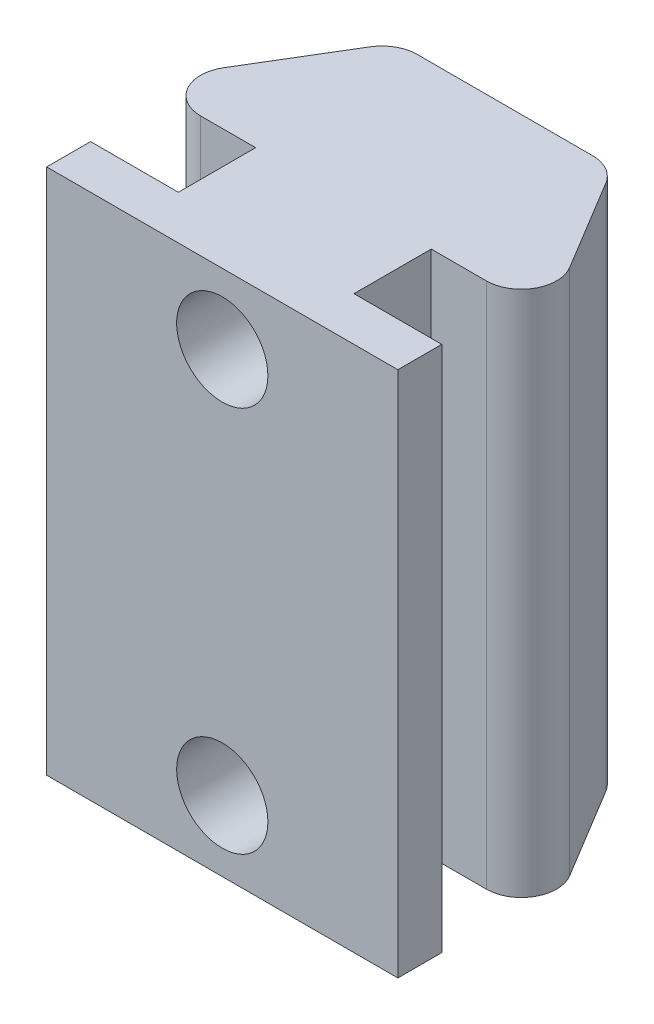
SolidWorks part; units mm, degrees
ref_plane "Front Plane" through (0, 0, 0) normal (0, 0, 1) x (1, 0, 0)
ref_plane "Top Plane" through (0, 0, 0) normal (0, 1, 0) x (1, 0, 0)
ref_plane "Right Plane" through (0, 0, 0) normal (1, 0, 0) x (0, 0, -1)
sketch "Sketch1" plane through (0, 0, 0) normal (0, 0, 1) x (1, 0, 0)
  line L0 (-6.35, 0) -> (6.35, 0) construction
  line L1 (-6.35, -9.525) -> (6.35, -9.525)
  line L2 (-6.35, -9.525) -> (-6.35, 9.525)
  line L3 (-6.35, 9.525) -> (6.35, 9.525)
  line L4 (6.35, -9.525) -> (6.35, 9.525)
  line L5 (-6.35, -9.525) -> (6.35, 9.525) construction
  line L6 (-6.35, 9.525) -> (6.35, -9.525) construction
  line L8 (-6.35, 9.525) -> (0, 9.525)
  point P0 (0, 0)
  dimension "D1" = 19.05
  dimension "D2" = 12.7
extrude "Boss-Extrude1" add sketch "Sketch1" along normal blind 1.5875 contours L2 L1 L4 L3
sketch "Sketch2" plane through (0, 9.525, 0) normal (0, 1, 0) x (1, 0, 0)
  line L0 (0, 0) -> (0, 8.636) construction
  line L1 (3.175, 0) -> (3.175, 2.794)
  line L2 (-6.35, 0) -> (6.35, 0) construction
  line L3 (3.175, 2.794) -> (5.1673, 2.794)
  line L4 (6.2547, 4.7201) -> (4.2624, 8.0221)
  line L5 (3.175, 8.636) -> (-3.175, 8.636)
  line L6 (3.175, 0) -> (-3.175, 0)
  line L7 (-3.175, 0) -> (-3.175, 2.794)
  line L8 (-3.175, 2.794) -> (-5.1673, 2.794)
  line L9 (-6.2547, 4.7201) -> (-4.2624, 8.0221)
  arc A0 (4.2624, 8.0221) -> (3.175, 8.636) centre (3.175, 7.366) ccw
  arc A1 (5.1673, 2.794) -> (6.2547, 4.7201) centre (5.1673, 4.064) ccw
  arc A2 (-5.1673, 2.794) -> (-6.2547, 4.7201) centre (-5.1673, 4.064) cw
  arc A3 (-4.2624, 8.0221) -> (-3.175, 8.636) centre (-3.175, 7.366) cw
  point P19 (3.892, 8.636)
  point P22 (7.4168, 2.794)
  point P25 (-7.4168, 2.794)
  point P28 (-3.892, 8.636)
  dimension "D5" = 1.27
  dimension "D1" = 8.636
  dimension "D2" = 6.35
  dimension "D3" = 5.842
  dimension "D4" = 14.8336
extrude "Boss-Extrude2" add sketch "Sketch2" against normal up to surface (19.05 mm away) up to face at (0, -9.525, 0.7937)
sketch "Sketch4" plane through (0, 0, 1.5875) normal (0, 0, 1) x (1, 0, 0)
  line L0 (-6.35, 0) -> (6.35, 0) construction
  line L1 (-6.35, -9.525) -> (-6.35, 9.525) construction
  line L2 (6.35, -9.525) -> (6.35, 9.525) construction
  line L3 (-6.35, 9.525) -> (6.35, 9.525) construction
  circle A0 centre (0, 6.985) radius 1.65
  circle A1 centre (0, -6.985) radius 1.65
  dimension "D1" = 3.3
  dimension "D2" = 2.54
extrude "Cut-Extrude1" cut sketch "Sketch4" against normal up to surface (4.3815 mm away) up to face at (4.1711, 0, -2.794)
